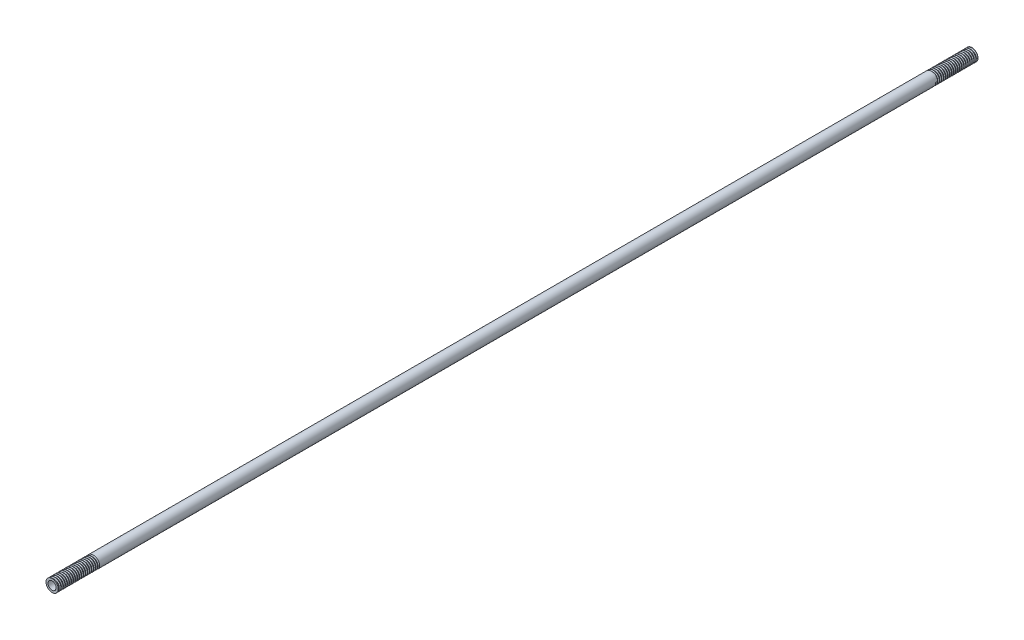
SolidWorks part; units mm, degrees
material "镀铬不锈钢"
ref_plane "前视基准面" through (0, 0, 0) normal (0, 0, 1) x (1, 0, 0)
ref_plane "上视基准面" through (0, 0, 0) normal (0, 1, 0) x (1, 0, 0)
ref_plane "右视基准面" through (0, 0, 0) normal (1, 0, 0) x (0, 0, -1)
sketch "草图1" plane through (0, 0, 0) normal (0, 0, 1) x (1, 0, 0)
  circle A0 centre (0, 0) radius 3
  dimension "D1" = 6
extrude "凸台-拉伸1" add sketch "草图1" along normal blind 453
thread "螺纹线1" pitch 1 method cut profile "螺纹线轮廓1" start angle 0, offset 0, length 20, pitch 1, diameter 6
ref_plane "基准面1" through (3, 0, 0) normal (0, -1, 0) x (1, 0, 0)
sketch "螺纹线轮廓1" plane through (3, 0, 0) normal (0, -1, 0) x (1, 0, 0)
  line L0 (0, 0) -> (0, 1) construction
  line L11 (0, 0) -> (0, 0.875)
  line L12 (0, 0.875) -> (-0.5413, 0.5625)
  line L13 (-0.5413, 0.5625) -> (-0.5413, 0.3125)
  line L15 (-0.5413, 0.3125) -> (0, 0)
  line L17 (-0.5413, 0.4375) -> (0, 0.4375) construction
  point P2 (0, 0)
  dimension "Pitch" = 1
  dimension "Profile_Angle" = 60
  dimension "Profile_Land" = 0.25
  dimension "Profile_Height" = 0.5413
thread "螺纹线2" pitch 1 method cut profile "螺纹线轮廓2" start angle 0, offset 0, length 20, pitch 1, diameter 6
ref_plane "基准面2" through (-3, 0, 453) normal (0, -1, 0) x (-1, 0, 0)
sketch "螺纹线轮廓2" plane through (-3, 0, 453) normal (0, -1, 0) x (-1, 0, 0)
  line L0 (0, 0) -> (0, 1) construction
  line L11 (0, 0) -> (0, 0.875)
  line L12 (0, 0.875) -> (-0.5413, 0.5625)
  line L13 (-0.5413, 0.5625) -> (-0.5413, 0.3125)
  line L15 (-0.5413, 0.3125) -> (0, 0)
  line L17 (-0.5413, 0.4375) -> (0, 0.4375) construction
  point P2 (0, 0)
  dimension "Pitch" = 1
  dimension "Profile_Angle" = 60
  dimension "Profile_Land" = 0.25
  dimension "Profile_Height" = 0.5413
sketch "草图2" plane through (0, 0, 453) normal (0, 0, 1) x (1, 0, 0)
  circle A0 centre (0, 0) radius 2
  dimension "D1" = 4
extrude "切除-拉伸1" cut sketch "草图2" against normal through all
